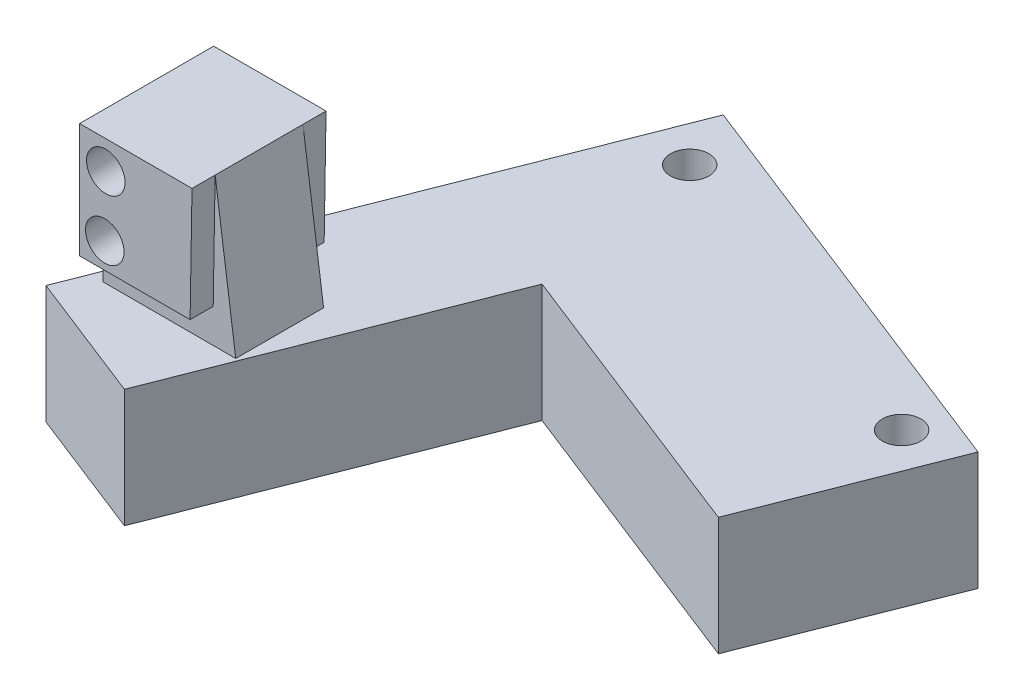
SolidWorks part; units mm, degrees
ref_plane "Front Plane" through (0, 0, 0) normal (0, 0, 1) x (1, 0, 0)
ref_plane "Top Plane" through (0, 0, 0) normal (0, 1, 0) x (1, 0, 0)
ref_plane "Right Plane" through (0, 0, 0) normal (1, 0, 0) x (0, 0, -1)
sketch "Sketch1" plane through (0, 0, 0) normal (0, 0, 1) x (1, 0, 0)
  line L0 (430.4818, 135.1883) -> (451.5463, 135.1883)
  line L1 (426.8731, 135.2483) -> (443.5981, 134.9701) construction
  line L2 (451.5463, 135.1883) -> (451.1391, 110.7021)
  line L3 (451.1391, 110.7021) -> (430.4818, 110.7021)
  line L4 (430.4818, 110.7021) -> (430.4818, 135.1883)
  line L5 (427.9702, 112.9511) -> (437.0368, 112.8004) construction
  line L6 (427.9702, 112.9511) -> (437.0368, 112.8004)
  line L7 (427.9702, 112.9511) -> (437.0368, 112.8004)
  line L8 (427.9702, 112.9511) -> (437.0368, 112.8004)
  line L9 (427.9702, 112.9511) -> (437.0368, 112.8004)
  line L10 (427.9702, 112.9511) -> (437.0368, 112.8004)
  arc A0 (444.3649, 127.3721) -> (443.5981, 134.9701) centre (437.3311, 130.5) ccw construction
  arc A1 (444.3649, 127.3721) -> (444.2998, 123.3969) centre (449.0067, 125.308) ccw construction
  arc A2 (443.2811, 115.8212) -> (444.2998, 123.3969) centre (437.1648, 120.5) ccw construction
  arc A3 (441.8282, 114.3719) -> (443.2811, 115.8212) centre (437.1648, 120.5) ccw construction
  arc A4 (437.0368, 112.8004) -> (441.8282, 114.3719) centre (437.1648, 120.5) ccw construction
  arc A5 (444.3649, 127.3721) -> (443.5981, 134.9701) centre (437.3311, 130.5) ccw
  arc A6 (444.3649, 127.3721) -> (444.2998, 123.3969) centre (449.0067, 125.308) ccw
  arc A7 (443.2811, 115.8212) -> (444.2998, 123.3969) centre (437.1648, 120.5) ccw
  arc A8 (441.8282, 114.3719) -> (443.2811, 115.8212) centre (437.1648, 120.5) ccw
  arc A9 (437.0368, 112.8004) -> (441.8282, 114.3719) centre (437.1648, 120.5) ccw
  circle A10 centre (437.3311, 130.5) radius 3.175
  circle A11 centre (437.1648, 120.5) radius 3.175
extrude "Boss-Extrude1" add sketch "Sketch1" along normal up to surface (22.098 mm away) contours L4 L3 L2 L0 A11 A10 region at (441.4313, 122.629, 0)
ref_plane "Plane1" through (0, 110.7021, 0) normal (0, 1, 0) x (1, 0, 0)
sketch "Sketch2" plane through (0, 110.7021, 0) normal (0, 1, 0) x (1, 0, 0)
  line L0 (460.3555, 56.6743) -> (529.4699, 29.5522)
  line L1 (529.4699, 29.5522) -> (517.4077, -1.1857)
  line L2 (517.4077, -1.1857) -> (469.5733, 17.5855)
  line L3 (469.5733, 17.5855) -> (450.1691, -31.8617)
  line L5 (428.889, -23.5109) -> (460.3555, 56.6743)
  line L7 (450.1691, -31.8617) -> (428.889, -23.5109)
  circle A0 centre (520.0432, 26.3896) radius 3.175
  circle A1 centre (464.7158, 46.7775) radius 3.175
  circle A2 centre (464.7158, 46.7775) radius 3.175 construction
  circle A3 centre (520.0432, 26.3896) radius 3.175 construction
  dimension "D5" = 7.62
  dimension "D9" = 6.35
  dimension "D10" = 6.35
  dimension "D2" = 22.86
  dimension "D3" = 33.02
  dimension "D4" = 7.62
  dimension "D6" = 74.2456
extrude "Boss-Extrude2" add sketch "Sketch2" against normal up to surface (19.4907 mm away)
sketch "Sketch3" plane through (430.4818, 0, 0) normal (-1, 0, 0) x (0, 0, 1)
  line L1 (0, 110.7021) -> (3.81, 110.7021)
  line L2 (0, 110.7021) -> (0, 116.2901)
  line L3 (0, 116.2901) -> (3.81, 116.2901)
  line L4 (3.81, 110.7021) -> (3.81, 116.2901)
  line L5 (22.098, 110.7021) -> (18.288, 110.7021)
  line L6 (22.098, 110.7021) -> (22.098, 116.2901)
  line L7 (22.098, 116.2901) -> (18.288, 116.2901)
  line L8 (18.288, 110.7021) -> (18.288, 116.2901)
  dimension "D1" = 3.81
  dimension "D2" = 3.81
  dimension "D3" = 5.588
  dimension "D4" = 5.588
extrude "Cut-Extrude1" cut sketch "Sketch3" against normal blind 28.702
sketch "Sketch4" plane through (0, 0, 0) normal (0, 0, -1) x (-1, 0, 0)
  line L0 (-430.4818, 135.1883) -> (-451.5463, 135.1883) construction
  line L1 (-433.0218, 135.1883) -> (-430.4818, 135.1883)
  line L2 (-433.0218, 135.1883) -> (-433.0218, 110.7021)
  line L3 (-433.0218, 110.7021) -> (-430.4818, 110.7021)
  line L4 (-430.4818, 135.1883) -> (-430.4818, 110.7021)
  line L5 (273.9292, 110.7021) -> (-273.9292, 110.7021) construction
  line L6 (-430.4818, 110.7021) -> (-430.4818, 116.2901) construction
  dimension "D1" = 2.54
extrude "Cut-Extrude2" cut sketch "Sketch4" against normal blind 28.702
ref_plane "Plane2" through (0, 0, 11.049) normal (0, 0, -1) x (-1, 0, 0)
sketch "Sketch7" plane through (0, 0, 11.049) normal (0, 0, -1) x (-1, 0, 0)
  line L0 (-451.5463, 135.1883) -> (-451.1391, 110.7021)
  line L1 (273.9292, 110.7021) -> (-273.9292, 110.7021) construction
  line L2 (-451.232, 116.2901) -> (-451.1391, 110.7021) construction
  line L3 (-451.1391, 110.7021) -> (-454.9491, 110.7021)
  line L4 (-454.9491, 110.7021) -> (-451.5463, 135.1883)
  dimension "D1" = 3.81
extrude "Boss-Extrude3" add sketch "Sketch7" along normal up to surface and the other way up to surface up to face at (441.007, 112.9373, 3.81) other way up to face at (442.1037, 113.4961, 18.288)
